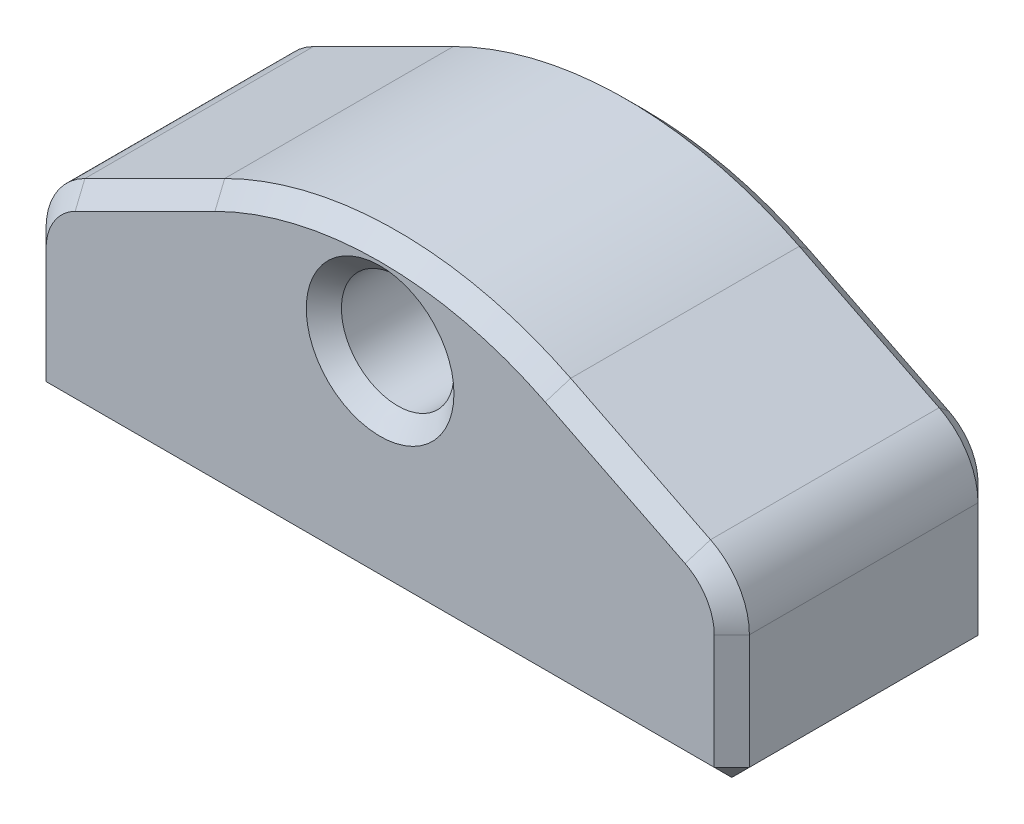
SolidWorks part; units mm, degrees
ref_plane "Front Plane" through (0, 0, 0) normal (0, 0, 1) x (1, 0, 0)
ref_plane "Top Plane" through (0, 0, 0) normal (0, 1, 0) x (1, 0, 0)
ref_plane "Right Plane" through (0, 0, 0) normal (1, 0, 0) x (0, 0, -1)
sketch "Sketch1" plane through (0, 0, 0) normal (0, 1, 0) x (1, 0, 0)
  line L0 (6.35, 0) -> (-6.35, 0) construction
  line L1 (12.7, 4.7625) -> (-12.7, 4.7625)
  line L2 (12.7, 4.7625) -> (12.7, -4.7625)
  line L3 (12.7, -4.7625) -> (-12.7, -4.7625)
  line L4 (-12.7, 4.7625) -> (-12.7, -4.7625)
  line L5 (12.7, 4.7625) -> (-12.7, -4.7625) construction
  line L6 (12.7, -4.7625) -> (-12.7, 4.7625) construction
  circle A0 centre (-6.35, 0) radius 2.032
  circle A1 centre (6.35, 0) radius 2.032
  point P0 (0, 0)
  point P9 (0, 0)
  dimension "D4" = 4.064
  dimension "D1" = 25.4
  dimension "D2" = 9.525
  dimension "D3" = 12.7
extrude "Boss-Extrude1" add sketch "Sketch1" along normal blind 12.7 contours L3 L4 L1 L2
extrude "Cut-Extrude1" cut sketch "Sketch1<3>" along normal blind 4.7625 contours A0 | A1 region at (-6.35, 0, 0) region at (6.35, 0, 0)
sketch "Sketch1<3>" plane through (0, 0, 0) normal (0, 1, 0) x (1, 0, 0) same geometry as "Sketch1"
sketch "Sketch3" plane through (0, 0, 4.7625) normal (0, 0, 1) x (1, 0, 0)
  line L0 (-12.7, 6.35) -> (0, 12.7)
  line L1 (-12.7, 12.7) -> (-12.7, 0) construction
  line L2 (0, 12.7) -> (12.7, 6.35)
  line L3 (12.7, 12.7) -> (12.7, 0) construction
  line L4 (12.7, 0) -> (-12.7, 0) construction
  circle A0 centre (0, 7.62) radius 2.032
  line M4 (12.7, 0) -> (12.7, 12.7)
  line M5 (12.7, 12.7) -> (-12.7, 12.7)
  line M6 (-12.7, 12.7) -> (-12.7, 0)
  dimension "D6" = 4.064
  dimension "D1" = 6.35
  dimension "D2" = 6.35
  dimension "D3" = 12.7
  dimension "D4" = 7.62
  dimension "D5" = 12.7
extrude "Cut-Extrude2" cut sketch "Sketch3" against normal through all contours L0 M6 M5 | L2 M5 M4 | A0 region at (-8.4667, 10.5833, 4.7625) region at (8.4667, 10.5833, 4.7625) region at (0, 7.62, 4.7625)
fillet "Fillet1" radius 13.97 1 edges at (0, 12.7, 0)
fillet "Fillet2" radius 2.54 2 edges at (12.7, 6.35, 0) (-12.7, 6.35, 0)
chamfer "Chamfer1" distance 0.635 angle 45 2 edges at (2.032, 7.62, 4.7625) (2.032, 7.62, -4.7625)
chamfer "Chamfer2" distance 0.635 angle 45 2 edges at (6.35, 0, 2.032) (-6.35, 0, 2.032)
chamfer "Chamfer3" distance 0.635 angle 45 18 edges at (-12.7, 2.3901, 4.7625) (-12.3207, 6.1156, 4.7625) (-8.7717, 8.3141, 4.7625) (12.7, 2.3901, 4.7625) (0, 11.0511, 4.7625) (12.3207, 6.1156, 4.7625) (8.7717, 8.3141, 4.7625) (12.7, 2.3901, -4.7625) (12.3207, 6.1156, -4.7625) (8.7717, 8.3141, -4.7625) (0, 11.0511, -4.7625) (-8.7717, 8.3141, -4.7625) (-12.3207, 6.1156, -4.7625) (-12.7, 2.3901, -4.7625) (12.7, 0, 0) (0, 0, -4.7625) (0, 0, 4.7625) (-12.7, 0, 0)
